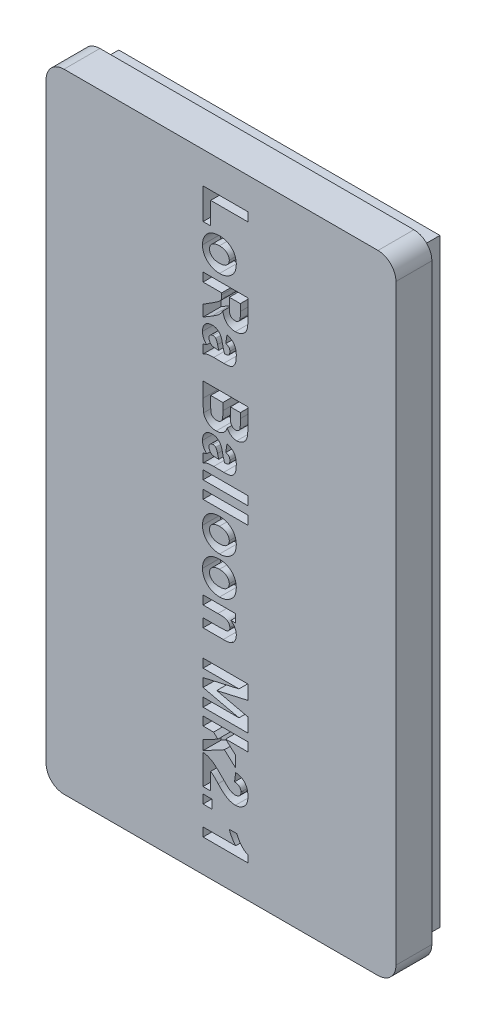
SolidWorks part; units mm, degrees
ref_plane "Front Plane" through (0, 0, 0) normal (0, 0, 1) x (1, 0, 0)
ref_plane "Top Plane" through (0, 0, 0) normal (0, 1, 0) x (1, 0, 0)
ref_plane "Right Plane" through (0, 0, 0) normal (1, 0, 0) x (0, 0, -1)
sketch "Sketch1" plane through (0, 0, 0) normal (0, 0, 1) x (1, 0, 0)
  line L1 (0, 0) -> (39, 0)
  line L2 (0, 0) -> (0, 70)
  line L3 (0, 70) -> (39, 70)
  line L4 (39, 0) -> (39, 70)
  dimension "D1" = 70
  dimension "D2" = 39
extrude "Boss-Extrude1" add sketch "Sketch1" along normal blind 4
sketch "Sketch2" plane through (0, 0, 0) normal (0, 0, -1) x (-1, 0, 0)
  line L0 (-39, 0) -> (-39, 70) construction
  line L1 (-37.4, 68.4) -> (-35.6, 68.4)
  line L2 (-37.4, 68.4) -> (-37.4, 1.6)
  line L3 (-37.4, 1.6) -> (-35.6, 1.6)
  line L4 (-35.6, 68.4) -> (-35.6, 1.6)
  line L5 (0, 0) -> (-39, 0) construction
  line L6 (0, 70) -> (0, 0) construction
  line L7 (-35.6, 1.6) -> (-1.6, 1.6)
  line L8 (-35.6, 1.6) -> (-35.6, 3.4)
  line L9 (-35.6, 3.4) -> (-1.6, 3.4)
  line L10 (-1.6, 1.6) -> (-1.6, 3.4)
  line L12 (-39, 70) -> (0, 70) construction
  line L13 (-39, 35) -> (0, 35) construction
  line L14 (-19.5, 70) -> (-19.5, 0) construction
  line L15 (-35.6, 66.6) -> (-1.6, 66.6)
  line L16 (-1.6, 68.4) -> (-1.6, 66.6)
  line L17 (-35.6, 68.4) -> (-1.6, 68.4)
  line L18 (-35.6, 68.4) -> (-35.6, 66.6)
  line L19 (-1.6, 1.6) -> (-3.4, 1.6)
  line L20 (-3.4, 68.4) -> (-3.4, 1.6)
  line L21 (-1.6, 68.4) -> (-3.4, 68.4)
  line L22 (-1.6, 68.4) -> (-1.6, 1.6)
  dimension "D1" = 1.6
  dimension "D2" = 1.8
  dimension "D3" = 1.6
  dimension "D4" = 1.8
extrude "Boss-Extrude2" add sketch "Sketch2" along normal blind 2.5 contours L4 L1 L2 L3 | L22 L15 L20 L9 | L20 L9 L4 L7 | L9 L20 L7 L10 | L17 L20 L15 L16 | L20 L17 L4 L15 region at (36.5, 35, 0) region at (19.5, 67.5, 0) region at (2.5, 67.5, 0) region at (19.5, 2.5, 0) region at (2.5, 35, 0) region at (2.5, 2.5, 0)
sketch "Sketch3" plane through (0, 0, 4) normal (0, 0, 1) x (1, 0, 0)
  line L0 (17.5, 0) -> (17.5, 67) construction
  line L4 (0, 0) -> (39, 0) construction
  line L6 (0, 70) -> (0, 0) construction
  text T0 "<b>LoRa Balloon Mk2.1</b>" font "Arial Narrow" height 5
  dimension "D1" = 17.5
  dimension "D2" = 67
extrude "Cut-Extrude1" cut sketch "Sketch3" against normal blind 2
fillet "Fillet1" radius 2 4 edges at (39, 70, 2) (39, 0, 2) (0, 0, 2) (0, 70, 2)
